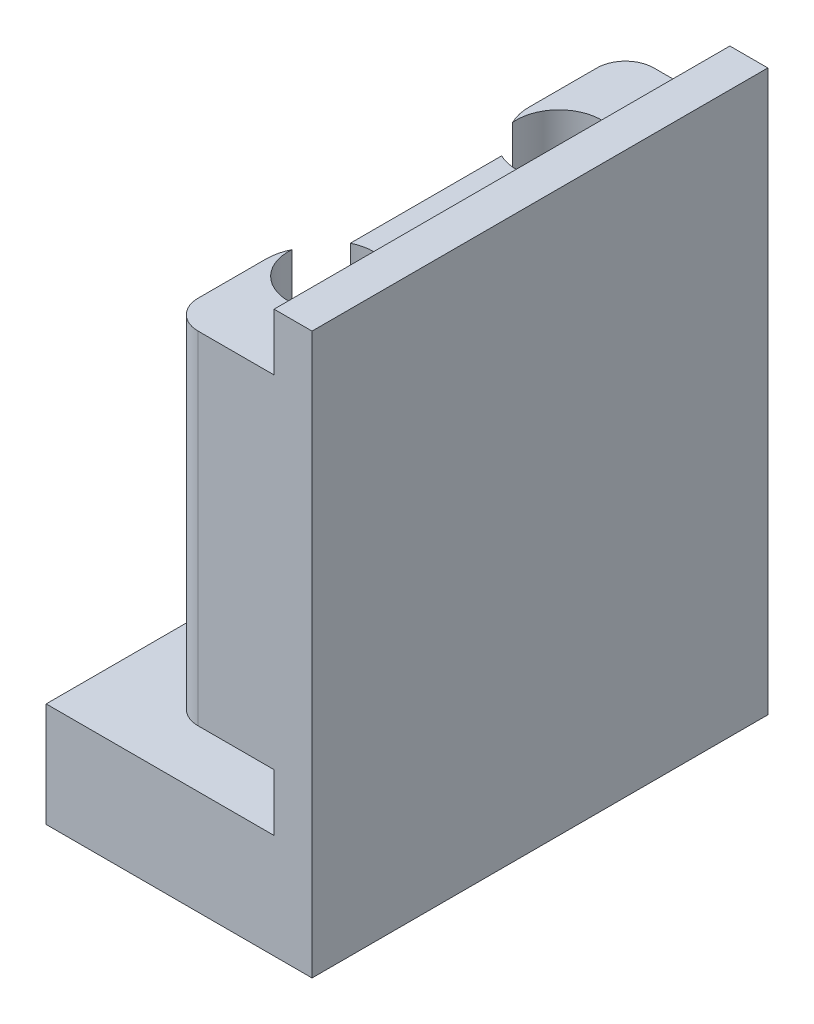
SolidWorks part; units mm, degrees
ref_plane "Front" through (0, 0, 0) normal (0, 0, 1) x (1, 0, 0)
ref_plane "Top" through (0, 0, 0) normal (0, 1, 0) x (1, 0, 0)
ref_plane "Right" through (0, 0, 0) normal (1, 0, 0) x (0, 0, -1)
sketch "Sketch1" plane through (0, 0, 0) normal (0, 1, 0) x (1, 0, 0)
  line L5 (-6, -12) -> (6, -12)
  line L6 (-6, -12) -> (-6, 12)
  line L7 (-6, 12) -> (6, 12)
  line L8 (6, -12) -> (6, 12)
  line L9 (-6, -12) -> (6, 12) construction
  line L10 (-6, 12) -> (6, -12) construction
  point P0 (0, 0)
  dimension "D1" = 12
  dimension "D2" = 24
extrude "Boss-Extrude1" add sketch "Sketch1" along normal blind 5.5
sketch "Sketch2" plane through (0, 0, 0) normal (0, 1, 0) x (1, 0, 0)
  line L0 (6, 12) -> (-6, 12) construction
  line L1 (6, -12) -> (8, -12)
  line L2 (6, -12) -> (6, 12)
  line L3 (6, 12) -> (8, 12)
  line L4 (8, -12) -> (8, 12)
  dimension "D1" = 2
extrude "Boss-Extrude2" add sketch "Sketch2" along normal blind 29.5
sketch "Sketch4" plane through (0, 5.5, 0) normal (0, 1, 0) x (1, 0, 0)
  line L1 (6, -12) -> (0.5, -12)
  line L2 (6, -12) -> (6, 12)
  line L3 (6, 12) -> (0.5, 12)
  line L4 (0.5, -12) -> (0.5, 12)
  line L5 (6, 12) -> (-6, 12) construction
  dimension "D1" = 5.5
extrude "Boss-Extrude4" add sketch "Sketch4" along normal blind 18 from offset 3
sketch "Sketch5" plane through (0.5, 0, 0) normal (-1, 0, 0) x (0, 0, 1)
  line L0 (-12, 26.5) -> (12, 26.5) construction
  line L1 (-4.625, 26.5) -> (4.625, 26.5)
  line L2 (-4.625, 26.5) -> (-4.625, 8.5)
  line L3 (-4.625, 8.5) -> (4.625, 8.5)
  line L4 (4.625, 26.5) -> (4.625, 8.5)
  line L5 (-12, 8.5) -> (12, 8.5) construction
  line L8 (4.625, 26.5) -> (12, 26.5) construction
  line L9 (-4.625, 26.5) -> (-12, 26.5) construction
  dimension "D1" = 9.25
extrude "Cut-Extrude1" cut sketch "Sketch5" against normal blind 1.5
fillet "Fillet1" radius 2.5 2 edges at (0.5, 17.5, 4.625) (0.5, 17.5, -4.625)
sketch "Sketch6" plane through (0, 26.5, 0) normal (0, 1, 0) x (1, 0, 0)
  line L1 (6, -12) -> (6, 12) construction
  line L3 (3, -12) -> (3, -6) construction
  line L4 (0.5, -12) -> (6, -12) construction
  line L5 (3, -6) -> (6, -6) construction
  line L7 (3, 12) -> (3, 6) construction
  line L9 (3, 6) -> (6, 6) construction
  line L10 (6, 12) -> (0.5, 12) construction
  circle A0 centre (3, -6) radius 2.25
  circle A4 centre (3, 6) radius 2.25
  dimension "D3" = 4.5
  dimension "D8" = 4.5
  dimension "D1" = 6
  dimension "D2" = 3
  dimension "D6" = 6
  dimension "D7" = 3
extrude "Cut-Extrude2" cut sketch "Sketch6" against normal through all
fillet "Fillet2" radius 1.5 2 edges at (0.5, 17.5, -12) (0.5, 17.5, 12)
